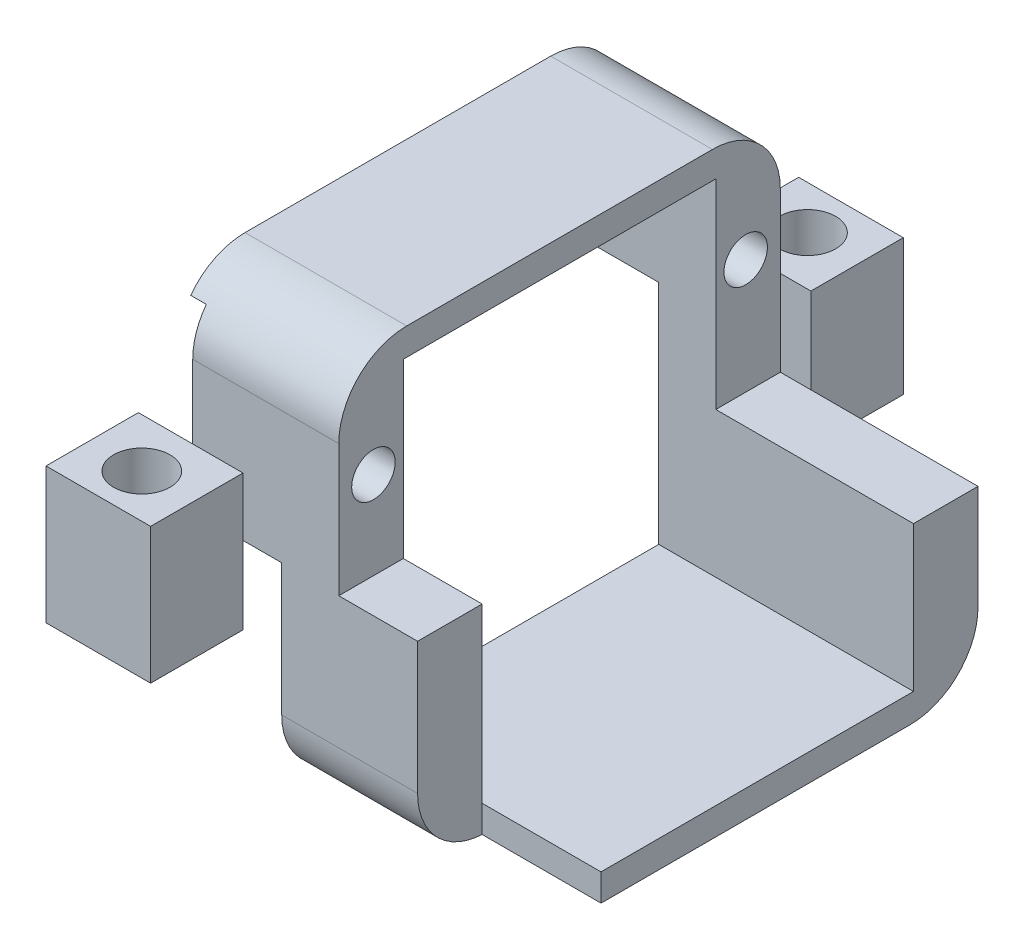
SolidWorks part; units mm, degrees
ref_plane "Front Plane" through (0, 0, 0) normal (0, 0, 1) x (1, 0, 0)
ref_plane "Top Plane" through (0, 0, 0) normal (0, 1, 0) x (1, 0, 0)
ref_plane "Right Plane" through (0, 0, 0) normal (1, 0, 0) x (0, 0, -1)
sketch "Sketch1" plane through (0, 0, 0) normal (0, 1, 0) x (1, 0, 0)
  line L0 (-1.1, 16.25) -> (-1.1, 11.5)
  line L1 (-17.65, -16.25) -> (17.65, -16.25)
  line L2 (-17.65, -16.25) -> (-17.65, 16.25)
  line L3 (-17.65, 16.25) -> (17.65, 16.25)
  line L4 (17.65, -16.25) -> (17.65, 16.25)
  line L5 (-17.65, -16.25) -> (17.65, 16.25) construction
  line L6 (-17.65, 16.25) -> (17.65, -16.25) construction
  line L7 (-1.1, 11.5) -> (17.65, 11.5)
  line L8 (-1.1, -16.25) -> (-1.1, -11.5)
  line L9 (-1.1, -11.5) -> (17.65, -11.5)
  line L10 (-1.1, 11.5) -> (-1.1, -11.5) construction
  line L11 (8.9, -11.5) -> (8.9, -16.25)
  line L12 (-8.8, 16.25) -> (-8.8, 11.5)
  line L13 (-8.8, 11.5) -> (-3.8, 11.5)
  line L14 (-3.8, 11.5) -> (-3.8, 16.25)
  line L15 (-3.8, -16.25) -> (-3.8, -11.5)
  line L16 (-3.8, -11.5) -> (-8.8, -11.5)
  line L17 (-8.8, -11.5) -> (-8.8, -16.25)
  line L18 (-8.8, 11.5) -> (-8.8, -11.5)
  line L19 (5.35, 16.25) -> (5.35, 23.05)
  line L20 (5.35, 23.05) -> (-2.35, 23.05)
  line L21 (-2.35, 23.05) -> (-2.35, 16.25)
  line L22 (-11.65, -16.25) -> (-11.65, -23.05)
  line L23 (-11.65, -23.05) -> (-3.95, -23.05)
  line L24 (-3.95, -23.05) -> (-3.95, -16.25)
  line L25 (9.53, -16.25) -> (9.53, -23.05)
  line L26 (9.53, -23.05) -> (17.23, -23.05)
  line L27 (17.23, -23.05) -> (17.23, -16.25)
  line L28 (-1.1, 11.5) -> (-1.1, -11.5)
  circle A0 centre (1.5, 19.85) radius 2.075
  circle A1 centre (13.38, -19.85) radius 2.075
  circle A2 centre (-7.8, -19.85) radius 2.075
  point P0 (0, 0)
  point P11 (-1.1, 0)
  point P31 (1.5, 23.05)
  point P45 (-7.8, -23.05)
  point P48 (13.38, -23.05)
  dimension "D11" = 4.15
  dimension "D18" = 4.15
  dimension "D19" = 4.15
  dimension "D1" = 32.5
  dimension "D2" = 23
  dimension "D3" = 8.75
  dimension "D4" = 10
  dimension "D5" = 16.55
  dimension "D6" = 2.7
  dimension "D7" = 5
  dimension "D8" = 1.5
  dimension "D9" = 7.7
  dimension "D10" = 6.8
  dimension "D12" = 9.85
  dimension "D13" = 31.03
  dimension "D14" = 7.7
  dimension "D15" = 19.85
  dimension "D16" = 7.7
  dimension "D17" = 6.8
  dimension "D20" = 19.85
extrude "Boss-Extrude1" add sketch "Sketch1" against normal blind 2 contours L7 L28 L9 L4 | L0 L7 L4 L3 | L11 L9 L8 L1 region at (8.275, 0, -13.875) region at (8.275, 0, 0) region at (3.9, 0, 13.875)
extrude "Boss-Extrude2" add sketch "Sketch1<3>" along normal blind 12.7 contours L0 L7 L4 L3 | L11 L9 L8 L1 region at (8.275, 0, -13.875) region at (3.9, 0, 13.875)
sketch "Sketch1<3>" plane through (0, 0, 0) normal (0, 1, 0) x (1, 0, 0) same geometry as "Sketch1"
sketch "Sketch3" plane through (0, 0, 0) normal (0, 1, 0) x (1, 0, 0)
  line L0 (3.1, 16.25) -> (3.1, 11.5)
  line L1 (-17.65, 16.25) -> (17.65, 16.25) construction
  line L2 (-1.1, 11.5) -> (17.65, 11.5) construction
  line L3 (3.1, 11.5) -> (-17.65, 11.5)
  line L4 (-17.65, -16.25) -> (-17.65, 16.25) construction
  line L5 (3.1, -16.25) -> (3.1, -11.5)
  line L6 (-17.65, -16.25) -> (17.65, -16.25) construction
  line L7 (-1.1, -11.5) -> (17.65, -11.5) construction
  line L8 (3.1, -11.5) -> (-17.65, -11.5)
  line L9 (3.1, 11.5) -> (3.1, -11.5)
  line L10 (-7.65, -11.5) -> (-7.65, -16.275)
  line L11 (3.1, 16.25) -> (-17.65, 16.25)
  line L12 (-17.65, 16.25) -> (-17.65, 11.5)
  line L13 (-17.65, -11.5) -> (-17.65, -16.25)
  line L14 (-17.65, -16.25) -> (3.1, -16.25)
  line L15 (-8.8, 11.5) -> (-8.8, -11.5)
  line L16 (-8.8, 11.5) -> (-8.8, 16.25)
  line L17 (-8.8, -11.5) -> (-8.8, -16.25)
  dimension "D1" = 20.75
  dimension "D2" = 10
extrude "Boss-Extrude3" add sketch "Sketch3" along normal blind 12.7 from surface contours L11 L12 L3 L0 | L10 L14 L5 L8 region at (-2.85, 0, -13.875) region at (-2.275, 0, 13.875) starting at face at (8.275, 12.7, -13.875)
extrude "Boss-Extrude4" add sketch "Sketch3<3>" along normal blind 2 from surface contours L16 L3 L0 L11 | L3 L15 L8 L9 | L10 L14 L5 L8 | L8 L17 L14 L10 region at (-2.85, 0, -13.875) region at (-2.85, 0, 0) region at (-2.275, 0, 13.875) region at (-8.225, 0, 13.875) starting at face at (-2.275, 25.4, 13.875)
sketch "Sketch3<3>" plane through (0, 0, 0) normal (0, 1, 0) x (1, 0, 0) same geometry as "Sketch3"
sketch "Sketch2" plane through (0, 0, 0) normal (1, 0, 0) x (0, 0, -1)
  line L0 (13.7, 6.45) -> (-13.7, 6.45) construction
  line L1 (-13.7, 19.15) -> (13.7, 19.15) construction
  circle A0 centre (13.7, 6.45) radius 1.6
  circle A1 centre (-13.7, 6.45) radius 1.6
  circle A2 centre (-13.7, 19.15) radius 1.6
  circle A3 centre (13.7, 19.15) radius 1.6
  point P4 (0, 6.45)
  dimension "D1" = 3.2
  dimension "D2" = 3.2
  dimension "D6" = 3.2
  dimension "D7" = 3.2
  dimension "D3" = 27.4
  dimension "D4" = 6.45
  dimension "D5" = 6.45
extrude "Cut-Extrude1" cut sketch "Sketch2" along normal blind 8 from surface contours A1 | A0 region at (0, 6.45, -13.7) region at (0, 6.45, 13.7) starting at face at (-1.1, 5.85, 0)
extrude "Cut-Extrude2" cut sketch "Sketch2<3>" against normal blind 8 from surface contours A3 | A2 region at (0, 19.15, 13.7) region at (0, 19.15, -13.7) starting at face at (3.1, 19.55, 0)
sketch "Sketch2<3>" plane through (0, 0, 0) normal (1, 0, 0) x (0, 0, -1) same geometry as "Sketch2"
extrude "Boss-Extrude5" add sketch "Sketch1<4>" along normal blind 10 from offset 7 contours L20 L21 L3 L19 A0 | L23 L24 L1 L22 A2 region at (-1.725, 0, -16.3527) region at (-4.0527, 0, 19.65)
sketch "Sketch1<4>" plane through (0, 0, 0) normal (0, 1, 0) x (1, 0, 0) same geometry as "Sketch1"
fillet "Fillet1" radius 5 4 edges at (3.9, -2, 16.25) (-2.85, 27.4, 16.25) (8.275, -2, -16.25) (-2.85, 27.4, -16.25)
sketch "Sketch5" plane through (0, 0, 0) normal (0, 1, 0) x (1, 0, 0)
  line L1 (17.65, 16.25) -> (3.1, 16.25)
  line L2 (17.65, 16.25) -> (17.65, 11.5)
  line L3 (17.65, 11.5) -> (3.1, 11.5)
  line L4 (3.1, 16.25) -> (3.1, 11.5)
extrude "Cut-Extrude3" cut sketch "Sketch5" against normal blind 2 from surface starting at face at (9.37, 12.7, -14.35)
sketch "Sketch6" plane through (0, 0, 0) normal (0, 1, 0) x (1, 0, 0)
  line L1 (-8.8, 11.5) -> (-1.1, 11.5)
  line L2 (-8.8, 11.5) -> (-8.8, 16.25)
  line L3 (-8.8, 16.25) -> (-1.1, 16.25)
  line L4 (-1.1, 11.5) -> (-1.1, 16.25)
extrude "Cut-Extrude4" cut sketch "Sketch6" along normal blind 4 from surface starting at face at (-4.43, 12.7, -14.35)
